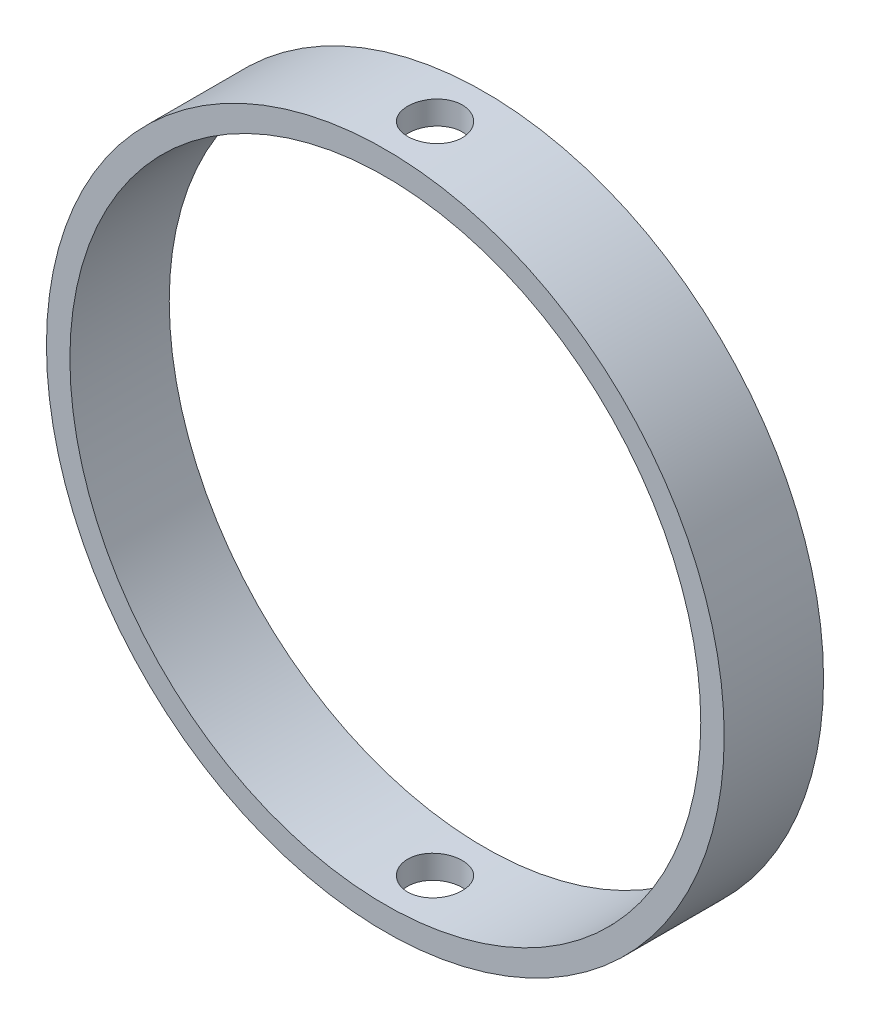
SolidWorks part; units mm, degrees
ref_plane "Front Plane" through (0, 0, 0) normal (0, 0, 1) x (1, 0, 0)
ref_plane "Top Plane" through (0, 0, 0) normal (0, 1, 0) x (1, 0, 0)
ref_plane "Right Plane" through (0, 0, 0) normal (1, 0, 0) x (0, 0, -1)
sketch "Sketch1" plane through (0, 0, 0) normal (0, 0, 1) x (1, 0, 0)
  circle A0 centre (0, 0) radius 34.11
  circle A1 centre (0, 0) radius 31.75
  dimension "D1" = 68.22
  dimension "D2" = 63.5
extrude "Boss-Extrude1" add sketch "Sketch1" along normal blind 10
ref_plane "Plane1" through (0, 34.11, 0) normal (0, 1, 0) x (1, 0, 0)
sketch "Sketch2" plane through (0, 34.11, 0) normal (0, 1, 0) x (1, 0, 0)
  circle A0 centre (0, -5) radius 2.75
  point P2 (0, 0)
  dimension "D1" = 5.5
  dimension "D2" = 5
extrude "Cut-Extrude1" cut sketch "Sketch2" against normal through all
